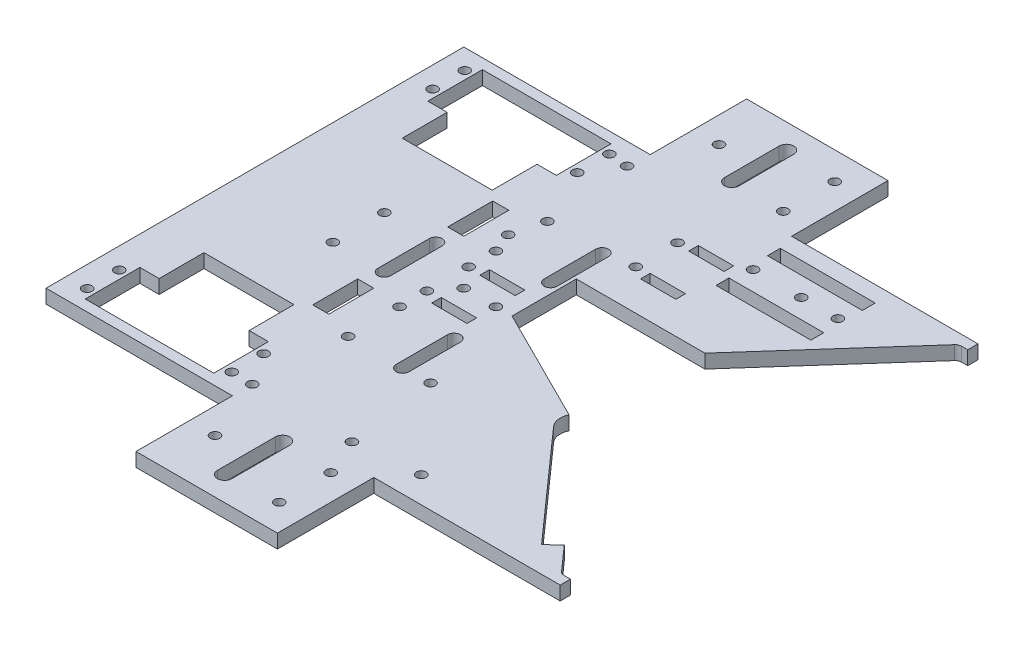
SolidWorks part; units mm, degrees
material "Acrylic (Medium-high impact)"
ref_plane "Front Plane" through (0, 0, 0) normal (0, 0, 1) x (1, 0, 0)
ref_plane "Top Plane" through (0, 0, 0) normal (0, 1, 0) x (1, 0, 0)
ref_plane "Right Plane" through (0, 0, 0) normal (1, 0, 0) x (0, 0, -1)
sketch "Sketch2" plane through (0, 0, 0) normal (0, 1, 0) x (1, 0, 0)
  line L2 (0, 0) -> (0, 65)
  line L3 (0, 65) -> (58, 65)
  line L4 (160, 0) -> (160, 65)
  line L8 (0, 0) -> (160, 0)
  line L9 (102, 65) -> (160, 65)
  line L11 (102, 65) -> (102, 95)
  line L12 (58, 65) -> (58, 95)
  line L13 (58, 95) -> (102, 95)
  dimension "D1" = 65
  dimension "D2" = 160
  dimension "D3" = 44
  dimension "D4" = 30
extrude "Boss-Extrude1" add sketch "Sketch2" along normal blind 4.3
mirror "Mirror1" about plane through (0, 4.3, 0) normal (0, 0, -1) of bodies 101
sketch "Sketch3" plane through (0, 4.3, 0) normal (0, 1, 0) x (1, 0, 0)
  line L0 (160, 61.8) -> (160, -61.8)
  line L1 (120.0126, 20) -> (157.1565, 61.8)
  line L3 (80.0126, 0) -> (80.0126, 20)
  line L4 (80.0126, 20) -> (120.0126, 20)
  line L12 (160, 65) -> (102, 65)
  line L13 (102, 65) -> (102, 95)
  line L15 (102, 95) -> (58, 95)
  line L16 (58, 65) -> (0, 65)
  line L17 (0, 65) -> (0, -65)
  line L18 (0, -65) -> (58, -65)
  line L20 (58, 95) -> (58, 65)
  line L22 (102, -65) -> (160, -65)
  line L23 (160, -65) -> (160, 65)
  line L36 (58, -65) -> (58, -95)
  line L38 (58, -95) -> (102, -95)
  line L39 (58, -95) -> (102, -95)
  line L40 (102, -95) -> (102, -65)
  line L42 (160, -61.8) -> (157.1556, -61.8)
  line L45 (160, 61.8) -> (157.1565, 61.8)
  line L48 (80.0126, 0) -> (120, -20)
  line L49 (120, -20) -> (157.1556, -61.8)
  line M24 (160, -65) -> (160, 65)
  dimension "D2" = 130
  dimension "D3" = 20
  dimension "D4" = 40
  dimension "D1" = 0
extrude "Cut-Extrude1" cut sketch "Sketch3" against normal blind 4.5 contours L48 L49 L1 L4 L3 M24 region at (132.7054, 4.3, -1.1594)
fillet "Fillet1" radius 2 2 edges at (157.1565, 2.15, -61.8) (157.1556, 2.15, 61.8)
ref_axis "Axis1" through (80, 4.3, 95) along (0, 0, -1)
sketch "Sketch4" plane through (0, 4.3, 0) normal (0, 1, 0) x (1, 0, 0)
  line L0 (80, -95) -> (80, 95)
  line L1 (102, -95) -> (58, -95) construction
  line L2 (102, 95) -> (58, 95) construction
ref_plane "Plane2" through (0, 4.3, 0) normal (0, 1, 0) x (1, 0, 0)
sketch "Sketch6" plane through (0, 4.3, 0) normal (0, 1, 0) x (1, 0, 0)
  line L3 (9, -61.8) -> (49, -61.8)
  line L6 (29, -45.8) -> (29, -44.8)
  line L7 (9, -44.8) -> (15, -44.8)
  line L11 (43, -44.8) -> (43, -30.8418)
  line L12 (15, -44.8) -> (15, -30.8418)
  line L13 (15, -30.8418) -> (43, -30.8418)
  line L15 (0, 0) -> (80.0126, 0)
  line L16 (80.0126, 0) -> (120, -20) construction
  line L18 (9, 44.8) -> (15, 44.8)
  line L20 (15, 30.8418) -> (43, 30.8418)
  line L21 (15, 44.8) -> (15, 30.8418)
  line L22 (43, 44.8) -> (43, 30.8418)
  line L25 (15, -45.8) -> (15, -30.8418) construction
  line L27 (9, 61.8) -> (49, 61.8)
  line L30 (4, -61.8) -> (3, -61.8)
  line L31 (0, -61.8) -> (160, -61.8) construction
  line L32 (3, -61.8) -> (4, -61.8)
  line L33 (3, -44.8) -> (3, -62.8) construction
  line L34 (3, -62.8) -> (55, -62.8) construction
  line L35 (55, -44.8) -> (55, -62.8) construction
  line L36 (4, -61.8) -> (54, -61.8) construction
  line L37 (0, 61.8) -> (160, 61.8) construction
  line L38 (54, 61.8) -> (55, 61.8)
  line L39 (54, 61.8) -> (55, 61.8)
  line L40 (43, 44.8) -> (49, 44.8)
  line L41 (4, -45.8) -> (4, -61.8) construction
  line L42 (4, -45.8) -> (54, -45.8) construction
  line L43 (43, -44.8) -> (49, -44.8)
  line L44 (3, -44.8) -> (55, -44.8) construction
  line L45 (29, -45.8) -> (29, -30.8418) construction
  line L46 (43, -45.8) -> (43, -30.8418) construction
  line L47 (54, -45.8) -> (54, -61.8) construction
  line L48 (9, -61.8) -> (49, -61.8)
  line L52 (9, 61.8) -> (9, 44.8)
  line L53 (55, 61.8) -> (54, 61.8)
  line L56 (49, 61.8) -> (49, 44.8)
  line L59 (3, -61.8) -> (4, -61.8)
  line L60 (9, -44.8) -> (9, -61.8)
  line L64 (49, -44.8) -> (49, -61.8)
  dimension "D4" = 1
  dimension "D5" = 14
  dimension "D6" = 14
extrude "Cut-Extrude2" cut sketch "Sketch6" against normal blind 10
sketch "Sketch8" plane through (0, 4.3, 0) normal (0, 1, 0) x (1, 0, 0)
  circle A0 centre (6.5, 58.8) radius 1.5
  circle A1 centre (6.5, 48.8) radius 1.5
  circle A2 centre (51.5, 48.8) radius 1.5
  circle A3 centre (51.5, 58.8) radius 1.5
  circle A4 centre (6.5, -48.7) radius 1.5
  circle A5 centre (6.5, -58.7) radius 1.5
  circle A6 centre (51.5, -58.7) radius 1.5
  circle A7 centre (51.5, -48.8) radius 1.5
  dimension "D7" = 3
extrude "Cut-Extrude3" cut sketch "Sketch8" against normal blind 10
sketch "Sketch9" plane through (0, 0, 0) normal (0, -1, 0) x (1, 0, 0)
  line L0 (75.75, 69.4) -> (75.75, 87.4)
  line L1 (75.75, -87.4) -> (75.75, -70.4)
  line L2 (80.25, -87.4) -> (80.25, -70.4)
  line L4 (80.25, 69.4) -> (80.25, 87.4)
  circle A0 centre (94, 70.4) radius 1.5
  circle A1 centre (66, 78.4) radius 1.5
  circle A2 centre (66, -78.4) radius 1.5
  circle A3 centre (94, -86.4) radius 1.5
  circle A4 centre (94, 86.4) radius 1.5
  circle A5 centre (94, -70.4) radius 1.5
  arc A6 (75.75, -87.4) -> (80.25, -87.4) centre (78, -87.4) ccw
  arc A7 (80.25, -70.4) -> (75.75, -70.4) centre (78, -70.4) ccw
  arc A10 (75.75, 69.4) -> (80.25, 69.4) centre (78, 69.4) ccw
  arc A12 (80.25, 87.4) -> (75.75, 87.4) centre (78, 87.4) ccw
  dimension "D1" = 3
extrude "Cut-Extrude4" cut sketch "Sketch9" against normal blind 10
sketch "Sketch7" plane through (0, 4.3, 0) normal (0, 1, 0) x (1, 0, 0)
  line L0 (0, 0) -> (80.0126, 0)
  line L1 (0, 65) -> (0, -65) construction
  line L2 (80.0126, 0) -> (80.0126, 20) construction
  line L3 (80, -95) -> (80, 95) construction
  line L4 (64, -9) -> (75, -9)
  line L5 (64, -6) -> (75, -6)
  line L6 (64, -9) -> (64, -6)
  line L7 (75, -9) -> (75, -6)
  line L8 (64, -7.5) -> (75, -7.5)
  line L9 (64, 7.5) -> (75, 7.5)
  line L10 (75, 9) -> (75, 6)
  line L11 (64, 9) -> (64, 6)
  line L12 (64, 6) -> (75, 6)
  line L13 (64, 9) -> (75, 9)
  line L14 (89.9874, 30) -> (100.9874, 30)
  line L15 (89.9874, 33) -> (100.9874, 33)
  line L16 (89.9874, 30) -> (89.9874, 33)
  line L17 (100.9874, 30) -> (100.9874, 33)
  line L20 (100.9874, 48) -> (100.9874, 45)
  line L21 (89.9874, 48) -> (89.9874, 45)
  line L22 (89.9874, 45) -> (100.9874, 45)
  line L23 (89.9874, 48) -> (100.9874, 48)
  line L24 (80.0126, 20) -> (120.0126, 20) construction
  circle A0 centre (60.0126, -6.5) radius 1.5
  circle A1 centre (60.0126, 6.5) radius 1.5
  circle A2 centre (86, 32.5) radius 1.5
  circle A3 centre (86, 45.5) radius 1.5
  dimension "D1" = 3
  dimension "D8" = 3
  dimension "D2" = 6.5
  dimension "D3" = 20
  dimension "D6" = 11
  dimension "D4" = 5
  dimension "D5" = 3
  dimension "D7" = 7.5
  dimension "D9" = 11
  dimension "D10" = 3
  dimension "D11" = 12
  dimension "D12" = 13
  dimension "D13" = 10
  dimension "D14" = 3.9874
  dimension "D15" = 0.5
  dimension "D16" = 0.5
  dimension "D17" = 3.9874
  dimension "D18" = 6
  dimension "D19" = 11
sketch "Sketch10" plane through (0, 4.3, 0) normal (0, 1, 0) x (1, 0, 0)
  line L0 (120, -20) -> (156.5589, -61.1287) construction
  line L1 (123.3218, -23.737) -> (149.8964, -53.6334)
  line L2 (116.263, -23.3218) -> (146.1593, -56.9552)
  line L3 (149.8964, -53.6334) -> (146.1593, -56.9552)
  line L4 (120, -20) -> (156.5589, -61.1287) construction
  line L5 (116.263, -23.3218) -> (152.8218, -64.4505) construction
  arc A0 (123.3218, -23.737) -> (116.263, -23.3218) centre (120, -20) ccw
  dimension "D1" = 5
  dimension "D2" = 45
extrude "Cut-Extrude5" cut sketch "Sketch10" against normal blind 10
sketch "Sketch11" plane through (0, 0, 0) normal (0, -1, 0) x (1, 0, 0)
  line L0 (0, 0) -> (80.0126, 0) construction
  line L1 (80, 95) -> (80, -95) construction
  line L2 (80.0126, 0) -> (0, 0)
  line L4 (75, 31.0313) -> (75, 15.0313)
  line L6 (79, 31.0313) -> (79, 15.0313)
  line L7 (79, -31.0313) -> (79, -15.0313)
  line L8 (75, -31.0313) -> (75, -15.0313)
  circle A0 centre (60, 31) radius 1.5
  circle A1 centre (60, 15) radius 1.5
  arc A2 (75, 31.0313) -> (79, 31.0313) centre (77, 31.0313) cw
  arc A3 (75, 15.0313) -> (79, 15.0313) centre (77, 15.0313) ccw
  arc A4 (75, -15.0313) -> (79, -15.0313) centre (77, -15.0313) cw
  arc A5 (75, -31.0313) -> (79, -31.0313) centre (77, -31.0313) ccw
  circle A6 centre (60, -15) radius 1.5
  circle A7 centre (60, -31) radius 1.5
  dimension "D1" = 3
  dimension "D2" = 16
  dimension "D3" = 15
  dimension "D4" = 20
  dimension "D5" = 15
  dimension "D6" = 4
extrude "Cut-Extrude6" cut sketch "Sketch11" against normal blind 10 contours L4 A3 L6 A2 | L8 A5 L7 A4 | A7 | A0 | A1 | A6 region at (77, 0, 23.0313) region at (77, 0, -23.0313) region at (60, 0, -31)
sketch "Sketch12" plane through (0, 0, 0) normal (0, -1, 0) x (-1, 0, 0)
  line L0 (0, 0) -> (-80.0126, 0) construction
  line L3 (-50.2627, -8) -> (-50.2627, 8)
  line L4 (-50.2627, 0) -> (-46.2627, 0)
  line L5 (-46.2627, -8) -> (-46.2627, 8)
  line L6 (0, 0) -> (-46.2627, 0)
  line L7 (0, 65) -> (0, -65) construction
  line L8 (-160, -61.8) -> (0, -61.8) construction
  line L9 (-80.0126, 0) -> (-50.2627, 0)
  line L10 (-80.0126, 0) -> (-115.5281, -17.7634) construction
  line L11 (-80.0126, 0) -> (-80.0126, 20) construction
  line L12 (-58, -65) -> (0, -65) construction
  line L13 (-58, 65) -> (0, 65) construction
  circle A0 centre (-32.2627, -8) radius 1.5
  circle A1 centre (-32.2627, 8) radius 1.5
  arc A2 (-46.2627, 8) -> (-50.2627, 8) centre (-48.2627, 8) ccw
  arc A3 (-50.2627, -8) -> (-46.2627, -8) centre (-48.2627, -8) ccw
  circle A5 centre (-32.2627, -8) radius 1.5 construction
  circle A6 centre (-32.2627, 8) radius 1.5 construction
  dimension "D1" = 3
  dimension "D8" = 8
  dimension "D9" = 8
  dimension "D2" = 8
  dimension "D3" = 14
  dimension "D4" = 4
  dimension "D5" = 61.8
  dimension "D6" = 65
  dimension "D7" = 65
extrude "Cut-Extrude7" cut sketch "Sketch12" against normal blind 10 contours A3 L5 L4 L3 | L4 L5 A2 L3 | A0 | A1 region at (48.2627, 0, 4.7958) region at (48.2627, 0, -4.7958) region at (32.2627, 0, 8) region at (32.2627, 0, -8)
extrude "Cut-Extrude8" cut sketch "Sketch7" against normal blind 9 contours A0 | L4 L7 L5 L6 | L12 L10 L13 L11 | A1 | L23 L20 L22 L21 | L15 L17 L14 L16 | A3 | A2
sketch "Sketch13" plane through (0, 4.3, 0) normal (0, 1, 0) x (1, 0, 0)
  line L0 (80.0126, 0) -> (59.0194, 0)
  line L1 (80, -95) -> (80, 95) construction
  circle A0 centre (65, 0) radius 1.5
  circle A1 centre (75, 0) radius 1.5
  dimension "D2" = 3
  dimension "D3" = 5
  dimension "D1" = 10
extrude "Cut-Extrude9" cut sketch "Sketch13" against normal blind 10 contours L0 A0 | L0 A0 | L0 A1 | L0 A1 region at (75, 4.3, 0.6366) region at (75, 4.3, -0.6366) region at (65, 4.3, 0.6366) region at (65, 4.3, -0.6366)
sketch "Sketch14" plane through (0, 4.3, 0) normal (0, 1, 0) x (1, 0, 0)
  line L0 (160, -65) -> (102, -65) construction
  line L1 (160, -65) -> (160, -61.8) construction
  circle A0 centre (57.5, 58.3) radius 1.5
  circle A2 centre (57.5, 21.3) radius 1.5
  circle A3 centre (85.37, -30.7129) radius 1.5
  circle A5 centre (108.6228, -56.8722) radius 1.5
  dimension "D1" = 3
  dimension "D2" = 3
  dimension "D5" = 3
  dimension "D3" = 34.2871
  dimension "D4" = 74.63
extrude "Cut-Extrude10" cut sketch "Sketch14" against normal blind 10
sketch "Sketch15" plane through (0, 4.3, 0) normal (0, 1, 0) x (1, 0, 0)
  line L1 (46, 28) -> (51, 28)
  line L2 (46, 28) -> (46, 14)
  line L3 (46, 14) -> (51, 14)
  line L4 (51, 28) -> (51, 14)
  line L6 (0, 65) -> (0, -65) construction
  line L7 (80.0126, 0) -> (53.7017, 0)
  line L8 (46, -14) -> (51, -14)
  line L9 (51, -28) -> (51, -14)
  line L10 (46, -28) -> (51, -28)
  line L11 (46, -28) -> (46, -14)
  arc A0 (50.2627, 8) -> (46.2627, 8) centre (48.2627, 8) ccw construction
  arc A1 (46.2627, -8) -> (50.2627, -8) centre (48.2627, -8) ccw construction
  dimension "D1" = 46
  dimension "D2" = 5
  dimension "D3" = 14
  dimension "D4" = 14
  dimension "D5" = 14
  dimension "D6" = 6
  dimension "D7" = 6
extrude "Cut-Extrude11" cut sketch "Sketch15" against normal blind 10 contours L4 L1 L2 L3 | L11 L10 L9 L8 region at (48.5, 4.3, -21) region at (48.5, 4.3, 21)
sketch "Sketch16" plane through (0, 4.3, 0) normal (0, 1, 0) x (1, 0, 0)
  circle A0 centre (89, -58.8) radius 1.5
  circle A1 centre (58, -58.8) radius 1.5
  dimension "D1" = 3
extrude "Cut-Extrude12" cut sketch "Sketch16" against normal blind 10
ref_plane "Plane3" through (44.2426, 0, 0) normal (1, 0, 0) x (0, 0, -1)
sketch "Sketch17" plane through (44.2426, 0, 0) normal (1, 0, 0) x (0, 0, -1)
  line L4 (0, 0) -> (20, 0)
  line L5 (20, 0) -> (20, 4.3)
  line L6 (20, 4.3) -> (0, 4.3)
  line L7 (0, 4.3) -> (0, 0)
  line L8 (0, 0) -> (20, 0)
  line L9 (20, 0) -> (20, 4.3)
  line L10 (20, 4.3) -> (0, 4.3)
  line L11 (0, 4.3) -> (0, 0)
  circle A0 centre (-2.83, 16.28) radius 0.5
  point P6 (0, 2.15)
  dimension "D4" = 1
  dimension "D2" = 2.83
  dimension "D3" = 14.13
  dimension "D1" = 0
sketch "Sketch18" plane through (0, 4.3, 0) normal (0, 1, 0) x (1, 0, 0)
  line L0 (121.5, 50) -> (129.9, 50)
  line L1 (103.5, 60) -> (133, 60)
  line L2 (102, 65) -> (102, 95) construction
  line L3 (160, 65) -> (102, 65) construction
  line L4 (103.5, 60) -> (103.5, 56)
  line L5 (106.5, 50) -> (118.5, 50)
  line L6 (133, 60) -> (133, 56)
  line L7 (103.5, 60) -> (133, 60)
  line L8 (103.5, 60) -> (103.5, 56)
  line L9 (103.5, 56) -> (133, 56)
  line L10 (133, 60) -> (133, 56)
  line L11 (103.5, 44) -> (133, 44)
  line L12 (133, 40) -> (133, 44)
  line L13 (103.5, 40) -> (133, 40)
  line L14 (103.5, 40) -> (103.5, 44)
  circle A0 centre (105, 50) radius 1.5
  circle A1 centre (120, 50) radius 1.5
  circle A3 centre (131.4, 50) radius 1.5
  dimension "D1" = 3
  dimension "D6" = 3
  dimension "D2" = 15
  dimension "D3" = 29.5
  dimension "D4" = 3
  dimension "D5" = 15
  dimension "D7" = 26.4
  dimension "D8" = 4
  dimension "D9" = 6
extrude "Cut-Extrude13" cut sketch "Sketch18" against normal blind 10 contours L4 L9 L6 L1 | A0 | A1 | A3 | L14 L13 L12 L11 region at (131.4, 4.3, -50) region at (120, 4.3, -50) region at (105, 4.3, -50) region at (118.25, 4.3, -58) region at (118.25, 4.3, -42)
